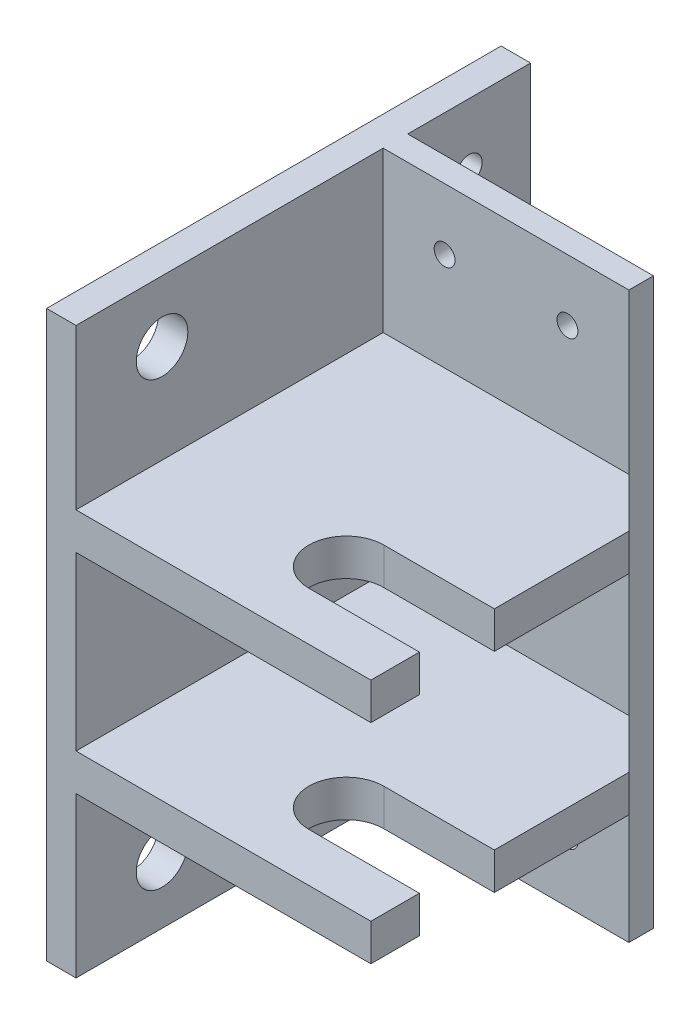
SolidWorks part; units mm, degrees
ref_plane "前视基准面" through (0, 0, 0) normal (0, 0, 1) x (1, 0, 0)
ref_plane "上视基准面" through (0, 0, 0) normal (0, 1, 0) x (1, 0, 0)
ref_plane "右视基准面" through (0, 0, 0) normal (1, 0, 0) x (0, 0, -1)
sketch "草图1" plane through (0, 0, 0) normal (0, 0, 1) x (1, 0, 0)
  line L0 (-87.1056, 0) -> (87.1056, 0) construction
  line L1 (0, 87.1056) -> (0, -87.1056) construction
  line L2 (100, -115) -> (-12, -115)
  line L3 (100, -115) -> (100, 115)
  line L4 (-12, -115) -> (-12, 115)
  line L5 (100, 115) -> (-12, 115)
  line L6 (100, -115) -> (-12, 115) construction
  line L7 (-12, -115) -> (100, 115) construction
  line L8 (0, 115) -> (0, -115)
  point P5 (44, 0)
  dimension "D1" = 100
  dimension "D2" = 12
  dimension "D3" = 230
extrude "凸台-拉伸1" add sketch "草图1" along normal blind 10 contours L5 L8 L2 L3 region at (50, 0, 0)
extrude "凸台-拉伸2" add sketch "草图1<3>" along normal blind 135 and the other way blind 50 contours L8 L5 L4 L2 region at (-6, 0, 0)
sketch "草图1<3>" plane through (0, 0, 0) normal (0, 0, 1) x (1, 0, 0) same geometry as "草图1"
sketch "草图2" plane through (0, 0, 0) normal (1, 0, 0) x (0, 0, -1)
  line L0 (-135, 115) -> (-135, -115) construction
  line L1 (-135, -50) -> (-10, -50)
  line L2 (-135, -50) -> (-135, -35)
  line L3 (-135, -35) -> (-10, -35)
  line L4 (-10, -50) -> (-10, -35)
  line L5 (-10, 115) -> (-10, -115) construction
  line L6 (-135, 0) -> (0, 0) construction
  line L7 (-135, 35) -> (-10, 35)
  line L8 (-135, 35) -> (-135, 50)
  line L9 (-135, 50) -> (-10, 50)
  line L10 (-10, 35) -> (-10, 50)
  dimension "D1" = 15
  dimension "D2" = 70
extrude "凸台-拉伸3" add sketch "草图2" along normal blind 120
sketch "草图3" plane through (0, 50, 0) normal (0, 1, 0) x (1, 0, 0)
  line L0 (120, -100) -> (75, -100) construction
  line L1 (120, -135) -> (120, -10) construction
  line L2 (120, -115.25) -> (75, -115.25)
  line L3 (120, -84.75) -> (75, -84.75)
  line L4 (100, 0) -> (0, 0) construction
  arc A0 (120, -115.25) -> (120, -84.75) centre (120, -100) ccw
  arc A1 (75, -84.75) -> (75, -115.25) centre (75, -100) ccw
  point P4 (97.5, -100)
  dimension "D1" = 30.5
  dimension "D2" = 100
  dimension "D3" = 45
extrude "切除-拉伸1" cut sketch "草图3" against normal through all
chamfer "倒角2" distance 20 angle 45 2 edges at (120, 42.5, 10) (120, -42.5, 10)
hole_wizard "孔3" positions "草图7" profile "草图6" legacy
sketch "草图7" plane through (0, 0, 0) normal (1, 0, 0) x (0, 0, -1)
  line L0 (-135, 0) -> (67.3388, 0) construction
  line L1 (-135, 35) -> (-135, -35) construction
  line L4 (0, 115) -> (0, -115) construction
  point P0 (-100, -90)
  point P1 (-100, 90)
  dimension "D1" = 180
  dimension "D2" = 100
sketch "草图6" plane through (0, -90, 100) normal (0, 1, 0) x (0, 0, -1)
  line L0 (0, 0) -> (0, 100)
  line L1 (0, 100) -> (10.5, 100)
  line L2 (10.5, 100) -> (10.5, 0)
  line L3 (10.5, 0) -> (0, 0)
  line L4 (0, 110) -> (0, -10) construction
  dimension "直径" = 21
  dimension "深度" = 100
hole_wizard "M10 螺纹孔1" positions "草图9" profile "草图10" tap size "M10" standard "GB"
sketch "草图9" plane through (0, 0, 10) normal (0, 0, 1) x (1, 0, 0)
  line L1 (75, 90) -> (25, 90) construction
  line L2 (75, 90) -> (75, -90) construction
  line L3 (75, -90) -> (25, -90) construction
  line L4 (25, 90) -> (25, -90) construction
  line L5 (75, 90) -> (25, -90) construction
  line L6 (75, -90) -> (25, 90) construction
  line L7 (0, 35) -> (0, -35) construction
  line L8 (25, 0) -> (75, 0) construction
  line L10 (0, 0) -> (75, 0) construction
  line L12 (0, -50) -> (0, -115) construction
  point P90 (25, -90)
  point P92 (75, -90)
  point P94 (75, 90)
  point P96 (25, 90)
  point P97 (75, 0)
  point P99 (25, 0)
  dimension "D1" = 75
  dimension "D2" = 50
  dimension "D3" = 180
sketch "草图10" plane through (25, -90, 10) normal (1, 0, 0) x (0, -1, 0)
  line L0 (0, 0) -> (0, 27.0537)
  line L1 (0, 27.0537) -> (4.25, 24.5)
  line L2 (4.25, 24.5) -> (4.25, 0)
  line L5 (4.25, 0) -> (0, 0)
  line L10 (0, 27.0537) -> (-4.25, 24.5) construction
  line L11 (0, -6.35) -> (0, 107.95) construction
  dimension "螺纹孔钻头直径" = 8.5
  dimension "螺纹孔钻头深度" = 24.5
  dimension "导头角度" = 118
cosmetic thread "孔螺蚊线3" parameters "D1"=10, "D2"=10
cosmetic thread "孔螺蚊线4" parameters "D1"=10, "D2"=10
cosmetic thread "孔螺蚊线5" parameters "D1"=10, "D2"=10
cosmetic thread "孔螺蚊线6" parameters "D1"=10, "D2"=10
cosmetic thread "孔螺蚊线7" parameters "D1"=10, "D2"=10
cosmetic thread "孔螺蚊线8" parameters "D1"=10, "D2"=10
hole_wizard "孔2" positions "草图12" profile "草图13" legacy
sketch "草图12" plane through (-12, 0, 0) normal (-1, 0, 0) x (0, 0, 1)
  line L0 (-50, 0) -> (135, 0) construction
  line L1 (-50, -115) -> (-50, 115) construction
  line L2 (135, -115) -> (135, 115) construction
  point P0 (-25, 90)
  point P1 (-25, -90)
  point P15 (-25, 0)
  dimension "D1" = 180
  dimension "D2" = 25
sketch "草图13" plane through (-12, 90, -25) normal (0, 1, 0) x (0, 0, 1)
  line L0 (0, 0) -> (0, 100)
  line L1 (0, 100) -> (5.25, 100)
  line L2 (5.25, 100) -> (5.25, 0)
  line L3 (5.25, 0) -> (0, 0)
  line L4 (0, 110) -> (0, -10) construction
  dimension "直径" = 10.5
  dimension "深度" = 100
